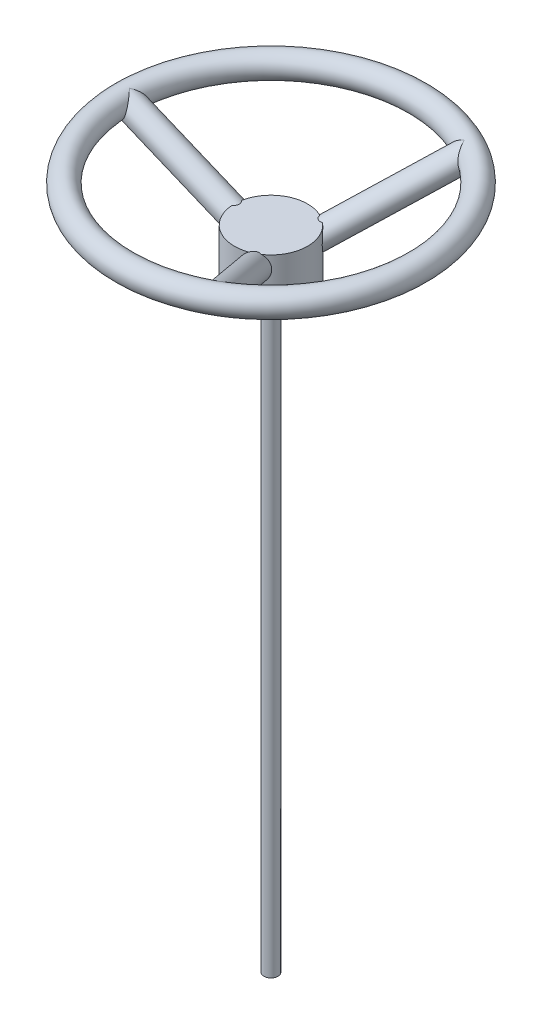
SolidWorks part; units mm, degrees
ref_plane "Front Plane" through (0, 0, 0) normal (0, 0, 1) x (1, 0, 0)
ref_plane "Top Plane" through (0, 0, 0) normal (0, 1, 0) x (1, 0, 0)
ref_plane "Right Plane" through (0, 0, 0) normal (1, 0, 0) x (0, 0, -1)
sketch "Sketch1" plane through (0, 0, 0) normal (0, 0, 1) x (1, 0, 0)
  line L0 (0, 0) -> (152.4, 0) construction
  line L1 (152.4, -24.1715) -> (152.4, 24.1715) construction
  circle A0 centre (0, 0) radius 12.7
  point P7 (152.4, 0)
  dimension "D1" = 25.4
  dimension "D2" = 152.4
revolve "Revolve1" add sketch "Sketch1" angle 360 about L1
sketch "Sketch3" plane through (0, 0, 0) normal (0, 1, 0) x (1, 0, 0)
  circle A0 centre (152.4, 0) radius 38.1 construction
  dimension "D1" = 76.2
  dimension "D2" = 152.4
ref_plane "Plane1" through (0, -38.1, 0) normal (0, 1, 0) x (1, 0, 0)
sketch "Sketch4" plane through (0, -38.1, 0) normal (0, 1, 0) x (1, 0, 0)
  circle A0 centre (152.4, 0) radius 38.1
extrude "Boss-Extrude1" add sketch "Sketch4" against normal blind 50.8 separate body
sketch3d "3DSketch1"
  line L0 (114.369, -50.8, -2.2918) -> (0, 0, 0)
  line L1 (114.369, -38.1, -2.2918) -> (114.369, -50.8, -2.2918) construction
  circle A0 centre (152.4, -38.1, 0) radius 38.1 construction
  point P5 (152.4, 0, 0)
  dimension "D1" = 12.7
sweep "Sweep1" add path "3DSketch1" circular profile diameter 25.4 parameters "D3"=25.4
sketch "Sketch13" plane through (114.369, -50.8, -2.2918) normal (0.9137, -0.4059, -0.0183) x (-0.0167, 0.0074, -0.9998)
  circle A0 centre (0, 0) radius 12.7
extrude "Boss-Extrude2" add sketch "Sketch13" along normal blind 50.8
pattern_circular "CirPattern1" count 3 over 360 about axis through (152.4, -38.1, 0) along (0, 1, 0) of "Sweep1", "Boss-Extrude2"
sketch "Sketch20" plane through (0, -88.9, 0) normal (0, -1, 0) x (-1, 0, 0)
  circle A0 centre (-152.4, 0) radius 7.3025
  dimension "D1" = 14.605
extrude "Boss-Extrude3" add sketch "Sketch20" along normal blind 622.3
